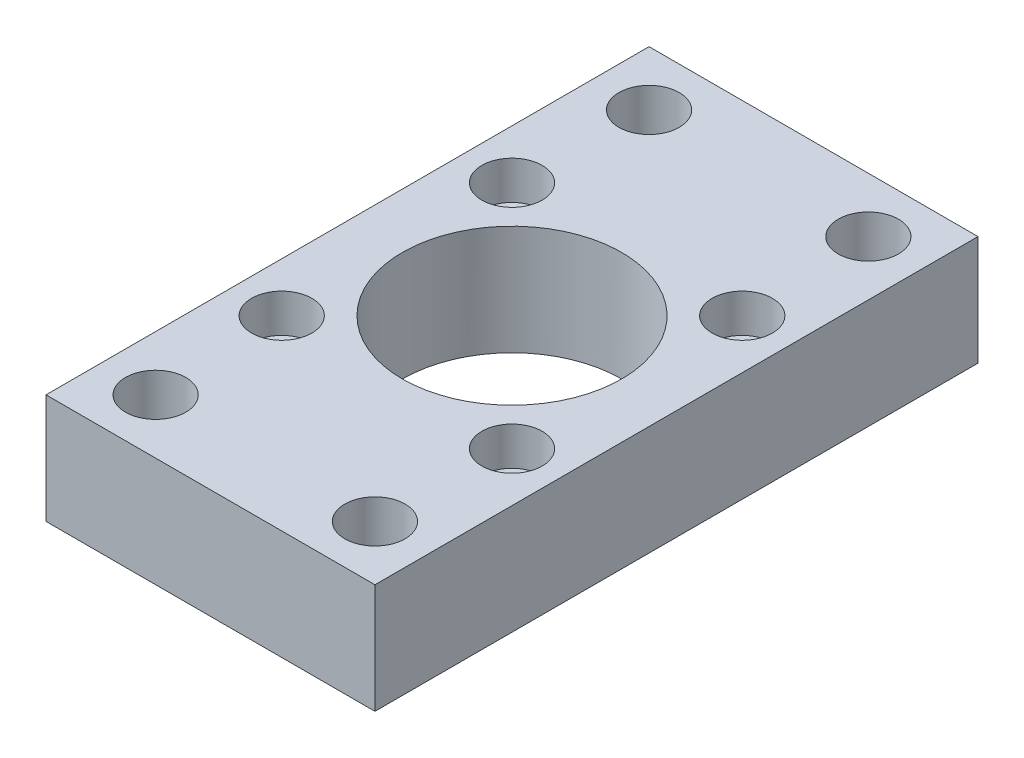
SolidWorks part; units mm, degrees
ref_plane "Alzado" through (0, 0, 0) normal (0, 0, 1) x (1, 0, 0)
ref_plane "Planta" through (0, 0, 0) normal (0, 1, 0) x (1, 0, 0)
ref_plane "Vista lateral" through (0, 0, 0) normal (1, 0, 0) x (0, 0, -1)
sketch "Croquis1" plane through (0, 0, 0) normal (1, 0, 0) x (0, 0, -1)
  line L0 (55, 0) -> (-55, 0)
  line L1 (-55, 0) -> (-55, -20)
  line L4 (-55, -20) -> (55, -20)
  line L7 (55, -20) -> (55, 0)
  dimension "D1" = 55
  dimension "D2" = 55
  dimension "D5" = 20
extrude "Saliente-Extruir1" add sketch "Croquis1" along normal blind 30 and the other way blind 30
sketch "Croquis2" plane through (0, 0, 0) normal (0, 1, 0) x (1, 0, 0)
  circle A0 centre (0, 0) radius 20
  dimension "D1" = 40
extrude "Cortar-Extruir1" cut sketch "Croquis2" against normal up to next contours A0
sketch "Croquis3" plane through (0, 0, 0) normal (0, 1, 0) x (1, 0, 0)
  circle A0 centre (-21, 21) radius 5.5
  circle A1 centre (21, 21) radius 5.5
  circle A2 centre (21, -21) radius 5.5
  circle A3 centre (-21, -21) radius 5.5
  dimension "D9" = 11
  dimension "D10" = 11
  dimension "D11" = 11
  dimension "D12" = 11
  dimension "D1" = 21
  dimension "D2" = 21
  dimension "D3" = 21
  dimension "D4" = 21
  dimension "D5" = 21
  dimension "D6" = 21
  dimension "D7" = 21
  dimension "D8" = 21
extrude "Cortar-Extruir2" cut sketch "Croquis3" against normal blind 7
sketch "Croquis4" plane through (0, -7, 0) normal (0, 1, 0) x (1, 0, 0)
  circle A0 centre (-21, 21) radius 3.25
  circle A1 centre (21, 21) radius 3.25
  circle A2 centre (21, -21) radius 3.25
  circle A3 centre (-21, -21) radius 3.25
  dimension "D1" = 6.5
  dimension "D2" = 6.5
  dimension "D3" = 6.5
  dimension "D4" = 6.5
extrude "Cortar-Extruir3" cut sketch "Croquis4" against normal up to next
sketch "Croquis5" plane through (0, 0, 0) normal (0, 1, 0) x (1, 0, 0)
  line L0 (-30, 55) -> (-30, -55) construction
  line L1 (30, 55) -> (30, -55) construction
  line L2 (-30, -55) -> (30, -55) construction
  line L3 (-30, 55) -> (30, 55) construction
  circle A0 centre (-20, 45) radius 5.5
  circle A1 centre (20, 45) radius 5.5
  circle A2 centre (20, -45) radius 5.5
  circle A3 centre (-20, -45) radius 5.5
  dimension "D1" = 10
  dimension "D2" = 10
  dimension "D3" = 10
  dimension "D4" = 11
  dimension "D5" = 10
  dimension "D6" = 10
  dimension "D7" = 10
  dimension "D8" = 11
  dimension "D9" = 11
  dimension "D10" = 11
  dimension "D11" = 10
  dimension "D12" = 10
extrude "Cortar-Extruir4" cut sketch "Croquis5" against normal up to next
